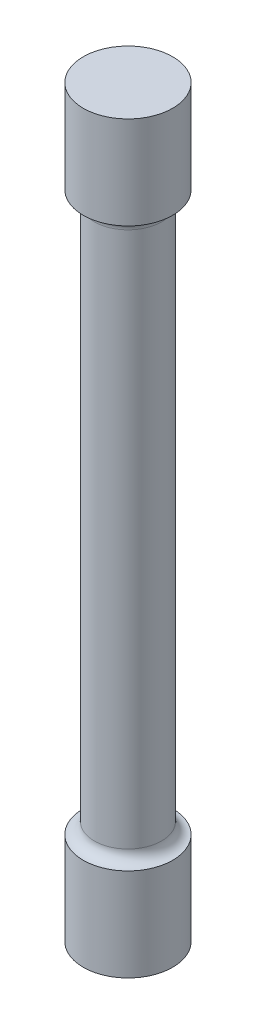
SolidWorks part; units mm, degrees
ref_plane "Alzado" through (0, 0, 0) normal (0, 0, 1) x (1, 0, 0)
ref_plane "Planta" through (0, 0, 0) normal (0, 1, 0) x (1, 0, 0)
ref_plane "Vista lateral" through (0, 0, 0) normal (1, 0, 0) x (0, 0, -1)
sketch "Croquis1" plane through (0, 0, 0) normal (0, 1, 0) x (1, 0, 0)
  circle A0 centre (0, 0) radius 2
  dimension "D1" = 4
extrude "Saliente-Extruir1" add sketch "Croquis1" along normal mid plane 33.3
sketch "Croquis2" plane through (0, 0, 0) normal (0, 1, 0) x (1, 0, 0)
  circle A0 centre (0, 0) radius 2
  circle A1 centre (0, 0) radius 1.505
  dimension "D1" = 3.01
  dimension "D2" = 4
extrude "Cortar-Extruir1" cut sketch "Croquis2" along direction (0, 1, 0) on the side against the normal blind 12.5 and the other way blind 12.5
fillet "Redondeo1" radius 0.5 1 edges at (0, -12.5, 1.505)
fillet "Redondeo2" radius 0.5 1 edges at (0, 12.5, 1.505)
